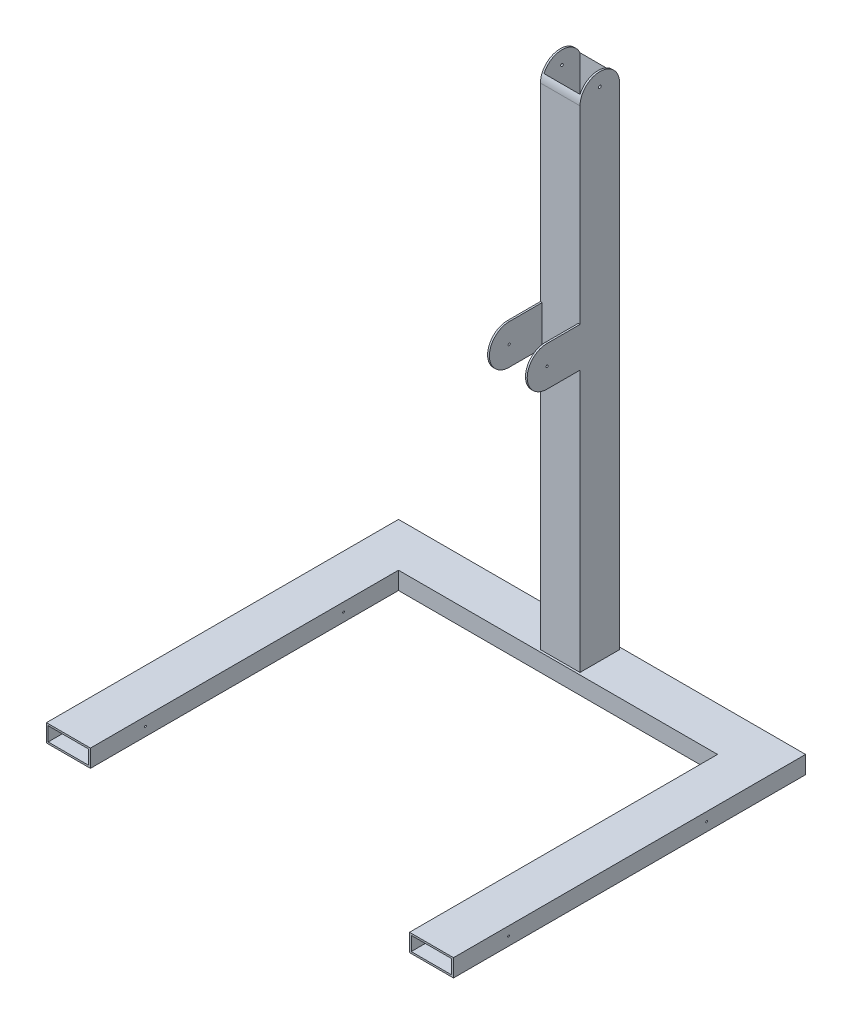
SolidWorks part; units mm, degrees
material "1.0036 (S235JRG1)"
ref_plane "Ön Düzlem" through (0, 0, 0) normal (0, 0, 1) x (1, 0, 0)
ref_plane "Üst Düzlem" through (0, 0, 0) normal (0, 1, 0) x (1, 0, 0)
ref_plane "Sağ Düzlem" through (0, 0, 0) normal (1, 0, 0) x (0, 0, -1)
sketch "Çizim1" plane through (0, 0, 0) normal (0, 0, 1) x (1, 0, 0)
  line L0 (0, 224.211) -> (0, -135.1343) construction
  line L1 (-925, 52.9522) -> (-725, 52.9522)
  line L2 (-925, 52.9522) -> (-925, -27.0478)
  line L3 (-925, -27.0478) -> (-725, -27.0478)
  line L4 (-725, 52.9522) -> (-725, -27.0478)
  line L5 (-733, 44.9522) -> (-917, 44.9522)
  line L6 (-733, 44.9522) -> (-733, -19.0478)
  line L7 (-733, -19.0478) -> (-917, -19.0478)
  line L8 (-917, 44.9522) -> (-917, -19.0478)
  line L9 (733, -19.0478) -> (917, -19.0478)
  line L10 (925, -27.0478) -> (725, -27.0478)
  line L11 (917, 44.9522) -> (917, -19.0478)
  line L12 (925, 52.9522) -> (925, -27.0478)
  line L13 (925, 52.9522) -> (725, 52.9522)
  line L14 (733, 44.9522) -> (917, 44.9522)
  line L15 (725, 52.9522) -> (725, -27.0478)
  line L16 (733, 44.9522) -> (733, -19.0478)
  dimension "D1" = 200
  dimension "D2" = 80
  dimension "D3" = 725
  dimension "D4" = 8
  dimension "D5" = 8
  dimension "D6" = 8
  dimension "D7" = 8
extrude "Yükseklik-Ekstrüzyon1" add sketch "Çizim1" against normal blind 1600
sketch "Çizim2" plane through (-725, 0, 0) normal (1, 0, 0) x (0, 0, -1)
  line L0 (1600, -27.0478) -> (0, -27.0478) construction
  line L1 (1600, 52.9522) -> (1400, 52.9522)
  line L2 (1600, 52.9522) -> (1600, -27.0478)
  line L3 (1600, -27.0478) -> (1400, -27.0478)
  line L4 (1400, 52.9522) -> (1400, -27.0478)
  line L6 (1592, 44.9522) -> (1408, 44.9522)
  line L7 (1592, 44.9522) -> (1592, -19.0478)
  line L8 (1592, -19.0478) -> (1408, -19.0478)
  line L9 (1408, 44.9522) -> (1408, -19.0478)
  dimension "D1" = 200
  dimension "D2" = 8
  dimension "D3" = 8
  dimension "D4" = 8
  dimension "D5" = 8
extrude "Yükseklik-Ekstrüzyon2" add sketch "Çizim2" along normal up to surface (1450 mm away) up to face at (725, 12.9522, -800)
sketch "Çizim3" plane through (0, 52.9522, 0) normal (0, 1, 0) x (1, 0, 0)
  line L0 (725, 1400) -> (-725, 1400) construction
  line L1 (-90, 1410) -> (90, 1410)
  line L2 (-90, 1410) -> (-90, 1590)
  line L3 (-90, 1590) -> (90, 1590)
  line L4 (90, 1410) -> (90, 1590)
  line L5 (-90, 1410) -> (90, 1590) construction
  line L6 (-90, 1590) -> (90, 1410) construction
  line L10 (82, 1582) -> (-82, 1582)
  line L11 (82, 1582) -> (82, 1418)
  line L12 (82, 1418) -> (-82, 1418)
  line L13 (-82, 1582) -> (-82, 1418)
  point P0 (0, 1500)
  point P11 (0, 1400)
  dimension "D1" = 180
  dimension "D2" = 180
  dimension "D3" = 10
  dimension "D4" = 8
  dimension "D5" = 8
extrude "Yükseklik-Ekstrüzyon3" add sketch "Çizim3" along normal blind 2320
sketch "Çizim4" plane through (-90, 0, 0) normal (-1, 0, 0) x (0, 0, 1)
  line L0 (-1410, 2372.9522) -> (-1410, 52.9522) construction
  line L1 (-1590, 2372.9522) -> (-1410, 2372.9522) construction
  line L2 (-1590, 2282.9522) -> (-1590, 2372.9522)
  line L3 (-1590, 2372.9522) -> (-1410, 2372.9522)
  line L4 (-1410, 2372.9522) -> (-1410, 2282.9522)
  circle A0 centre (-1500, 2312.9522) radius 6
  circle A1 centre (-1500, 2282.9522) radius 90
  line M2 (-1410, 52.9522) -> (-1410, 2372.9522)
  line M3 (-1410, 2372.9522) -> (-1590, 2372.9522)
  line M4 (-1590, 2372.9522) -> (-1590, 52.9522)
  dimension "D1" = 12
  dimension "D2" = 90
  dimension "D3" = 60
extrude "Kes-Ekstrüzyon1" cut sketch "Çizim4" against normal blind 180 contours A1 L3 M4 | A1 M2 M3 region at (-90, 2352.8491, -1569.8969) region at (-90, 2352.8491, -1430.1031)
extrude "Kes-Ekstrüzyon2" cut sketch "Çizim4<3>" against normal blind 180 contours A0
sketch "Çizim4<3>" plane through (-90, 0, 0) normal (-1, 0, 0) x (0, 0, 1) same geometry as "Çizim4"
sketch "Çizim5" plane through (-925, 0, 0) normal (-1, 0, 0) x (0, 0, 1)
  line L0 (-700, 52.9522) -> (-700, -27.0478) construction
  line L1 (-1600, 52.9522) -> (0, 52.9522) construction
  line L2 (-1600, -27.0478) -> (0, -27.0478) construction
  line L3 (0, 52.9522) -> (0, -27.0478) construction
  circle A0 centre (-250, 12.9522) radius 4
  circle A1 centre (-1150, 12.9522) radius 4
  dimension "D2" = 8
  dimension "D3" = 40
  dimension "D4" = 250
  dimension "D1" = 700
extrude "Kes-Ekstrüzyon3" cut sketch "Çizim5" against normal up to surface (1850 mm away) up to face at (925, 12.9522, -800)
sketch "Çizim6" plane through (-90, 0, 0) normal (-1, 0, 0) x (0, 0, 1)
  line L0 (-1410, 1422.9522) -> (-1260, 1422.9522)
  line L1 (-1410, 2282.9522) -> (-1410, 52.9522) construction
  line L2 (-1260, 1242.9522) -> (-1410, 1242.9522)
  line L3 (-1410, 1242.9522) -> (-1410, 1422.9522)
  arc A0 (-1260, 1422.9522) -> (-1260, 1242.9522) centre (-1260, 1332.9522) cw
  dimension "D2" = 90
  dimension "D3" = 150
  dimension "D1" = 950
extrude "Yükseklik-Ekstrüzyon4" add sketch "Çizim6" against normal blind 8
sketch "Çizim7" plane through (90, 0, 0) normal (1, 0, 0) x (0, 0, -1)
  line L0 (1410, 1422.9522) -> (1260, 1422.9522)
  line L1 (1260, 1242.9522) -> (1410, 1242.9522)
  line L2 (1410, 1242.9522) -> (1410, 1422.9522)
  arc A0 (1260, 1422.9522) -> (1260, 1242.9522) centre (1260, 1332.9522) ccw
extrude "Yükseklik-Ekstrüzyon5" add sketch "Çizim7" against normal blind 8
sketch "Çizim8" plane through (-90, 0, 0) normal (-1, 0, 0) x (0, 0, 1)
  circle A0 centre (-1260, 1332.9522) radius 5
  dimension "D1" = 10
extrude "Kes-Ekstrüzyon4" cut sketch "Çizim8" against normal blind 284
